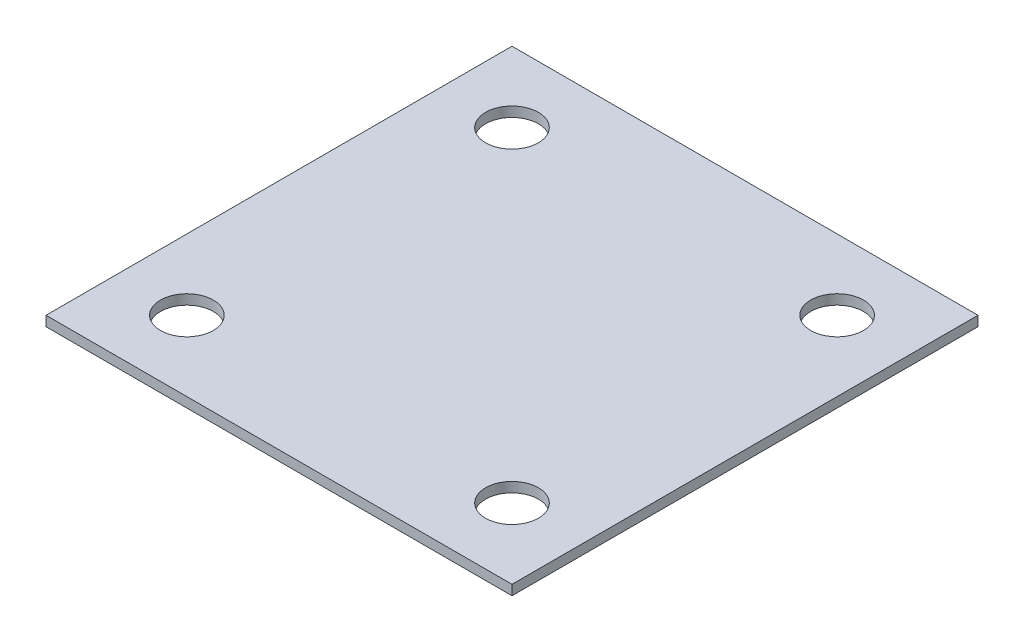
SolidWorks part; units mm, degrees
ref_plane "Front Plane" through (0, 0, 0) normal (0, 0, 1) x (1, 0, 0)
ref_plane "Top Plane" through (0, 0, 0) normal (0, 1, 0) x (1, 0, 0)
ref_plane "Right Plane" through (0, 0, 0) normal (1, 0, 0) x (0, 0, -1)
sketch "Sketch1" plane through (0, 0, 0) normal (0, 1, 0) x (1, 0, 0)
  line L1 (-37.5, -37.5) -> (37.5, -37.5)
  line L2 (-37.5, -37.5) -> (-37.5, 37.5)
  line L3 (-37.5, 37.5) -> (37.5, 37.5)
  line L4 (37.5, -37.5) -> (37.5, 37.5)
  line L5 (-37.5, -37.5) -> (37.5, 37.5) construction
  line L6 (-37.5, 37.5) -> (37.5, -37.5) construction
  circle A0 centre (-26.1629, -26.1629) radius 4.25
  circle A1 centre (26.1631, -26.1629) radius 4.25
  circle A2 centre (-26.1629, 26.1629) radius 4.25
  circle A3 centre (26.1631, 26.1629) radius 4.25
  point P0 (0, 0)
  dimension "D3" = 8.5
  dimension "D7" = 8.5
  dimension "D8" = 8.5
  dimension "D9" = 8.5
  dimension "D4" = 26.1629
  dimension "D6" = 26.1629
  dimension "D2" = 26.1629
  dimension "D1" = 75
  dimension "D5" = 74
extrude "Boss-Extrude1" add sketch "Sketch1" along normal blind 1.6
equation "\"width\"=26.1629"
equation "\"D2@Sketch1\"=\"width\""
equation "\"D6@Sketch1\"=\"width\""
equation "\"D4@Sketch1\"=\"width\""
